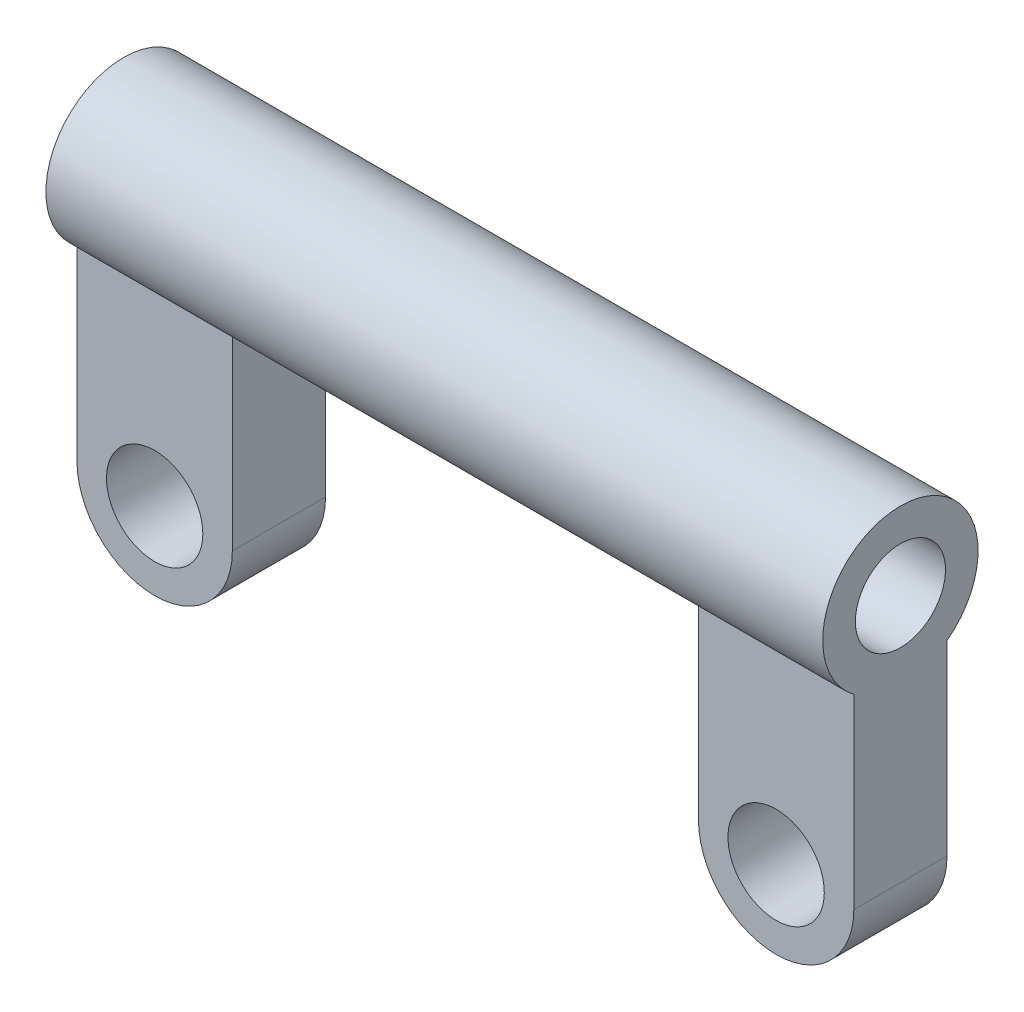
SolidWorks part; units mm, degrees
ref_plane "Front Plane" through (0, 0, 0) normal (0, 0, 1) x (1, 0, 0)
ref_plane "Top Plane" through (0, 0, 0) normal (0, 1, 0) x (1, 0, 0)
ref_plane "Right Plane" through (0, 0, 0) normal (1, 0, 0) x (0, 0, -1)
sketch "Sketch1" plane through (0, 0, 0) normal (0, 0, 1) x (1, 0, 0)
  line L0 (2.75, 0) -> (-2.75, 0) construction
  line L1 (0, 54.4262) -> (0, -50.2609) construction
  line L2 (0, -2.75) -> (0, 2.75) construction
  line L4 (-12.5, -2.5) -> (-7.5, -2.5)
  line L5 (-12.5, -2.5) -> (-12.5, 8)
  line L6 (-12.5, 8) -> (-7.5, 8)
  line L7 (-7.5, -2.5) -> (-7.5, 8)
  line L8 (7.5, -2.5) -> (12.5, -2.5)
  line L9 (7.5, -2.5) -> (7.5, 8)
  line L10 (7.5, 8) -> (12.5, 8)
  line L11 (12.5, -2.5) -> (12.5, 8)
  circle A0 centre (-10, 0) radius 1.55
  circle A1 centre (10, 0) radius 1.55
  point P19 (0, 0)
  dimension "D1" = 3.1
  dimension "D2" = 20
  dimension "D3" = 5
  dimension "D4" = 2.5
  dimension "D5" = 2.5
  dimension "D6" = 2.5
  dimension "D7" = 2.5
  dimension "D8" = 5
  dimension "D9" = 8
  dimension "D10" = 8
extrude "Boss-Extrude1" add sketch "Sketch1" along normal mid plane 3
sketch "Sketch2" plane through (-12.5, 0, 0) normal (-1, 0, 0) x (0, 0, 1)
  line L0 (1.5, 8) -> (-1.5, 8) construction
  circle A0 centre (0, 8) radius 2.5
  circle A1 centre (0, 8) radius 1.45
  line M4 (1.5, 8) -> (-1.5, 8)
  dimension "D1" = 5
  dimension "D2" = 2.9
extrude "Boss-Extrude2" add sketch "Sketch2" against normal up to surface (25 mm away) up to face at (12.5, 2.75, 0)
extrude "Cut-Extrude1" cut sketch "Sketch2<2>" against normal up to surface (25 mm away) contours A1 M4 region at (-12.5, 7.3846, 0) up to face at (12.5, 2.875, 0)
sketch "Sketch2<2>" plane through (-12.5, 0, 0) normal (-1, 0, 0) x (0, 0, 1) same geometry as "Sketch2"
fillet "Fillet1" radius 2.5 4 edges at (7.5, -2.5, 0) (-7.5, -2.5, 0) (-12.5, -2.5, 0) (12.5, -2.5, 0)
